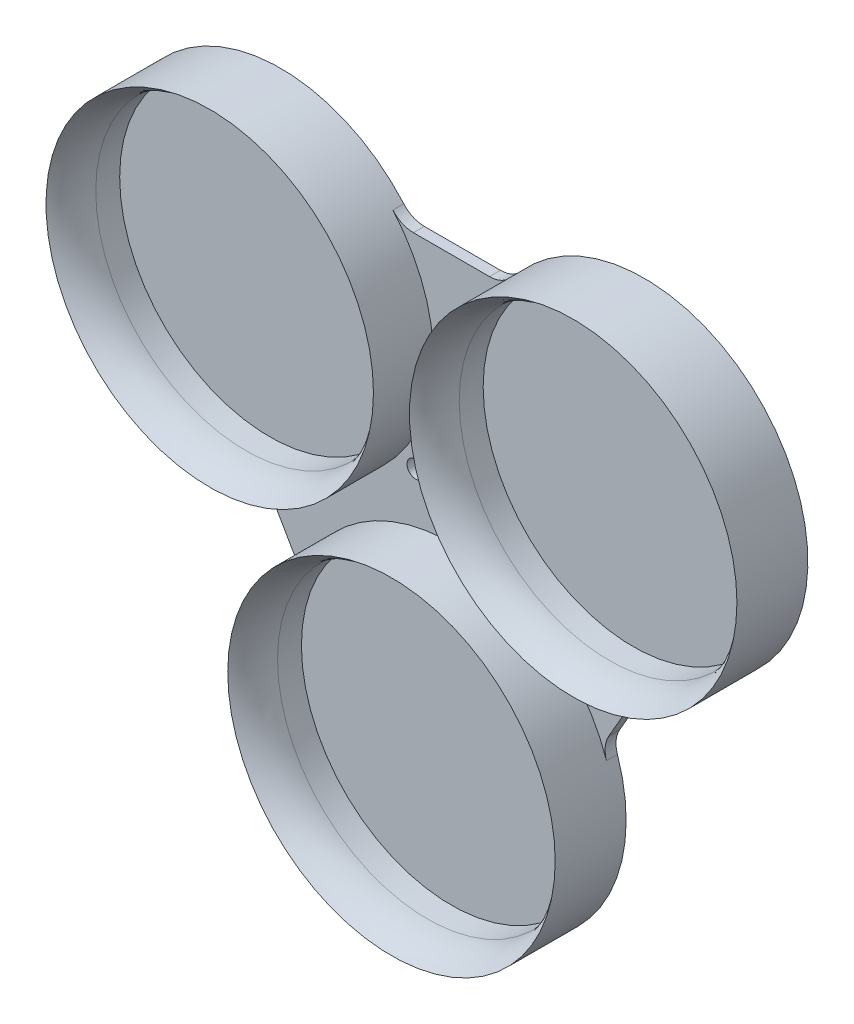
SolidWorks part; units mm, degrees
ref_plane "前视基准面" through (0, 0, 0) normal (0, 0, 1) x (1, 0, 0)
ref_plane "上视基准面" through (0, 0, 0) normal (0, 1, 0) x (1, 0, 0)
ref_plane "右视基准面" through (0, 0, 0) normal (1, 0, 0) x (0, 0, -1)
other "Configuration Table"
sketch "草图1" plane through (0, 0, 0) normal (0, 0, 1) x (1, 0, 0)
  line L0 (0, 0) -> (66.6, 0) construction
  line L1 (66.6, 0) -> (33.3, -57.6773) construction
  line L2 (33.3, -57.6773) -> (0, 0) construction
  circle A0 centre (0, 0) radius 27.5
  circle A1 centre (0, 0) radius 30
  circle A2 centre (66.6, 0) radius 30
  circle A3 centre (66.6, 0) radius 27.5
  circle A4 centre (33.3, -57.6773) radius 30
  circle A5 centre (33.3, -57.6773) radius 27.5
  dimension "D1" = 66.6
  dimension "D2" = 66.6
  dimension "D3" = 66.6
extrude "凸台-拉伸1" add sketch "草图1" along normal blind 13
sketch "草图2" plane through (0, 0, 0) normal (0, 0, 1) x (1, 0, 0)
  line L4 (26.3199, 18.0708) -> (40.2801, 18.0708)
  line L6 (69.0899, -31.8291) -> (62.1097, -43.919)
  line L8 (4.4903, -43.919) -> (-2.4899, -31.8291)
  arc A10 (22.5599, 19.775) -> (-5.8457, -29.425) centre (0, 0) ccw
  arc A11 (72.4457, -29.425) -> (44.0401, 19.775) centre (66.6, 0) ccw
  arc A12 (4.8944, -48.0273) -> (61.7056, -48.0273) centre (33.3, -57.6773) ccw
  arc A14 (4.8944, -48.0273) -> (4.4903, -43.919) centre (0.1601, -46.419) ccw
  arc A16 (-2.4899, -31.8291) -> (-5.8457, -29.425) centre (-6.82, -34.3291) ccw
  arc A17 (62.1097, -43.919) -> (61.7056, -48.0273) centre (66.4399, -46.419) ccw
  arc A18 (72.4457, -29.425) -> (69.0899, -31.8291) centre (73.42, -34.3291) ccw
  arc A19 (40.2801, 18.0708) -> (44.0401, 19.775) centre (40.2801, 23.0708) ccw
  arc A20 (26.3199, 18.0708) -> (22.5599, 19.775) centre (26.3199, 23.0708) cw
  dimension "D1" = 5
extrude "凸台-拉伸2" add sketch "草图2" along normal blind 2
sketch "草图3" plane through (0, 0, 0) normal (0, 0, 1) x (1, 0, 0)
  circle A0 centre (33.3, -57.6773) radius 27.5 construction
  circle A1 centre (66.6, 0) radius 27.5 construction
  circle A4 centre (33.3, -19.2258) radius 38.4515 construction
  circle A5 centre (33.3, -19.2258) radius 1.65
  circle A6 centre (33.3, -19.2258) radius 6.547 construction
  circle A7 centre (33.3, -12.6788) radius 1.6
  circle A8 centre (39.847, -19.2258) radius 1.6
  circle A9 centre (33.3, -25.7727) radius 1.6
  circle A10 centre (26.753, -19.2258) radius 1.6
  dimension "D1" = 13.0939
extrude "切除-拉伸5" cut sketch "草图3" along normal through all
fillet "圆角1" radius 10 3 edges at (94.1, 0, 13) (27.5, 0, 13) (60.8, -57.6773, 13)
